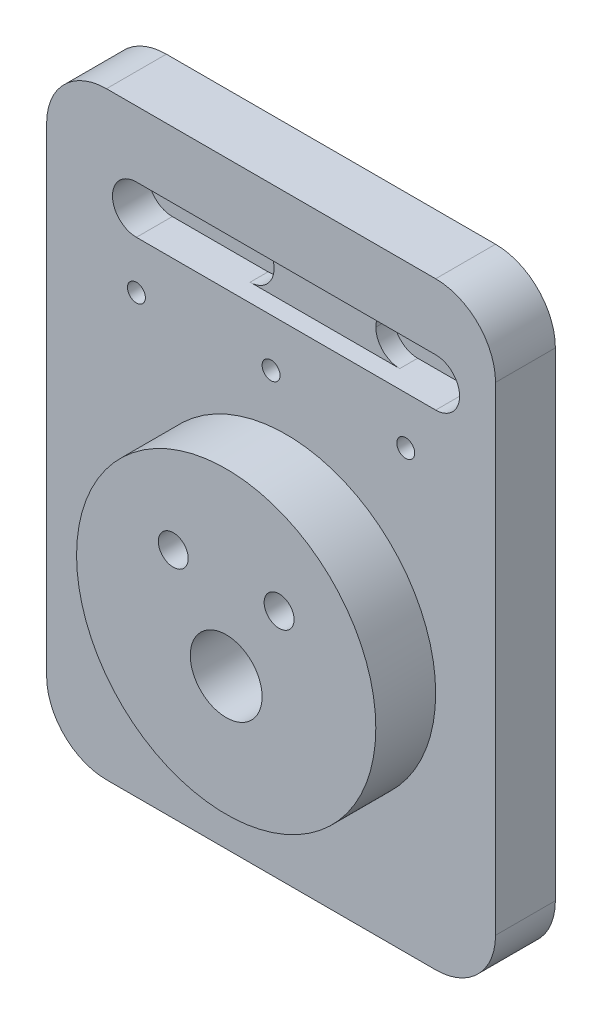
SolidWorks part; units mm, degrees
ref_plane "Front Plane" through (0, 0, 0) normal (0, 0, 1) x (1, 0, 0)
ref_plane "Top Plane" through (0, 0, 0) normal (0, 1, 0) x (1, 0, 0)
ref_plane "Right Plane" through (0, 0, 0) normal (1, 0, 0) x (0, 0, -1)
sketch "Sketch2" plane through (0, 0, 0) normal (0, 0, 1) x (1, 0, 0)
  line L1 (0, 0) -> (75, 0)
  line L2 (0, 0) -> (0, 100)
  line L3 (0, 100) -> (75, 100)
  line L4 (75, 0) -> (75, 100)
  dimension "D1" = 75
  dimension "D2" = 100
extrude "Boss-Extrude1" add sketch "Sketch2" along normal blind 10
sketch "Sketch5" plane through (0, 0, 10) normal (0, 0, 1) x (1, 0, 0)
  line L0 (75, 0) -> (75, 100) construction
  line L1 (0, 0) -> (75, 0) construction
  circle A0 centre (40, 40) radius 25
  dimension "D1" = 50
  dimension "D2" = 35
  dimension "D3" = 40
extrude "Boss-Extrude4" add sketch "Sketch5" along normal blind 10
sketch "Sketch6" plane through (0, 0, 20) normal (0, 0, 1) x (1, 0, 0)
  line L0 (15, 40) -> (65, 40) construction
  line L1 (40, 65) -> (40, 15) construction
  line L2 (40, 40) -> (22.3223, 57.6777) construction
  line L3 (40, 40) -> (57.6777, 57.6777)
  circle A0 centre (40, 40) radius 25 construction
  circle A1 centre (40, 40) radius 25 construction
  point P11 (31.1612, 48.8388)
  point P13 (40, 35)
  point P14 (48.8388, 48.8388)
  dimension "D1" = 45
  dimension "D2" = 45
  dimension "D3" = 5
hole_wizard "Ø5.0 (5) Diameter Hole1" positions "Sketch7" profile "Sketch8" hole size "Ø5.0" standard "AS" end condition through all
sketch "Sketch7" plane through (0, 0, 20) normal (0, 0, 1) x (1, 0, 0)
  point P0 (31.1612, 48.8388)
  point P3 (48.8388, 48.8388)
sketch "Sketch8" plane through (31.1612, 48.8388, 20) normal (1, 0, 0) x (0, -1, 0)
  line L0 (0, 0) -> (0, 20)
  line L1 (0, 20) -> (2.5, 20)
  line L2 (2.5, 20) -> (2.5, 0)
  line L5 (2.5, 0) -> (0, 0)
  line L11 (0, -6.35) -> (0, 107.95) construction
  dimension "Thru Hole Dia." = 5
  dimension "Thru Hole Depth" = 20
hole_wizard "Ø12.0 (12) Diameter Hole1" positions "Sketch9" profile "Sketch10" hole size "Ø12.0" standard "AS" end condition through all
sketch "Sketch9" plane through (0, 0, 20) normal (0, 0, 1) x (1, 0, 0)
  point P0 (40, 35)
sketch "Sketch10" plane through (40, 35, 20) normal (1, 0, 0) x (0, -1, 0)
  line L0 (0, 0) -> (0, 20)
  line L1 (0, 20) -> (6, 20)
  line L2 (6, 20) -> (6, 0)
  line L5 (6, 0) -> (0, 0)
  line L11 (0, -6.35) -> (0, 107.95) construction
  dimension "Thru Hole Dia." = 12
  dimension "Thru Hole Depth" = 20
sketch "Sketch12" plane through (0, 0, 10) normal (0, 0, 1) x (1, 0, 0)
  line L0 (15, 85) -> (65, 85) construction
  line L1 (15, 89) -> (65, 89)
  line L2 (15, 81) -> (65, 81)
  line L3 (75, 100) -> (0, 100) construction
  line L4 (40, 65) -> (40, 96.7105) construction
  arc A0 (15, 89) -> (15, 81) centre (15, 85) ccw
  arc A1 (65, 81) -> (65, 89) centre (65, 85) ccw
  point P2 (40, 85)
  dimension "D1" = 15
  dimension "D2" = 8
  dimension "D3" = 50
extrude "Cut-Extrude1" cut sketch "Sketch12" against normal blind 6
fillet "Fillet1" radius 10 4 edges at (0, 0, 5) (75, 0, 5) (75, 100, 5) (0, 100, 5)
sketch "Sketch13" plane through (0, 0, 10) normal (0, 0, 1) x (1, 0, 0)
  line L0 (0, 73) -> (75, 73) construction
  line L1 (0, 90) -> (0, 10) construction
  line L2 (75, 10) -> (75, 90) construction
  line L3 (65, 100) -> (10, 100) construction
  point P8 (15, 73)
  point P9 (60, 73)
  point P10 (37.5, 73)
  dimension "D1" = 27
  dimension "D2" = 15
  dimension "D3" = 15
hole_wizard "Ø3.0 (3) Diameter Hole1" positions "Sketch14" profile "Sketch15" hole size "Ø3.0" standard "AS"
sketch "Sketch14" plane through (0, 0, 10) normal (0, 0, 1) x (1, 0, 0)
  line L0 (0, 73) -> (75, 73) construction
  point P0 (15, 73)
  point P3 (37.5, 73)
  point P7 (60, 73)
sketch "Sketch15" plane through (15, 73, 10) normal (1, 0, 0) x (0, -1, 0)
  line L0 (0, 0) -> (0, 10.9013)
  line L1 (0, 10.9013) -> (1.5, 10)
  line L2 (1.5, 10) -> (1.5, 0)
  line L5 (1.5, 0) -> (0, 0)
  line L10 (0, 10.9013) -> (-1.5, 10) construction
  line L11 (0, -6.35) -> (0, 107.95) construction
  dimension "Hole Dia." = 3
  dimension "Hole Depth" = 10
  dimension "Drill Angle" = 118
sketch "Sketch16" plane through (0, 0, 10) normal (0, 0, 1) x (1, 0, 0)
  line L0 (24.3807, 5) -> (50.6193, 5) construction
  line L1 (37.5, 0) -> (37.5, 12.6493) construction
  line L2 (10, 0) -> (65, 0) construction
  text T0 "MAMAMOO"
  point P3 (37.5, 5)
  dimension "D1" = 5
sketch "Sketch18" plane through (0, 0, 4) normal (0, 0, 1) x (1, 0, 0)
  line L0 (40, 89) -> (40, 81) construction
  line L1 (65, 89) -> (15, 89) construction
  line L2 (15, 81) -> (65, 81) construction
  line L4 (35, 89) -> (52, 89)
  line L5 (35, 89) -> (35, 81)
  line L6 (35, 81) -> (52, 81)
  line L7 (52, 89) -> (52, 81)
  dimension "D1" = 5
  dimension "D2" = 12
extrude "Boss-Extrude5" add sketch "Sketch18" along normal blind 3
fillet "Fillet2" radius 4 4 edges at (52, 81, 5.5) (52, 89, 5.5) (35, 81, 5.5) (35, 89, 5.5)
